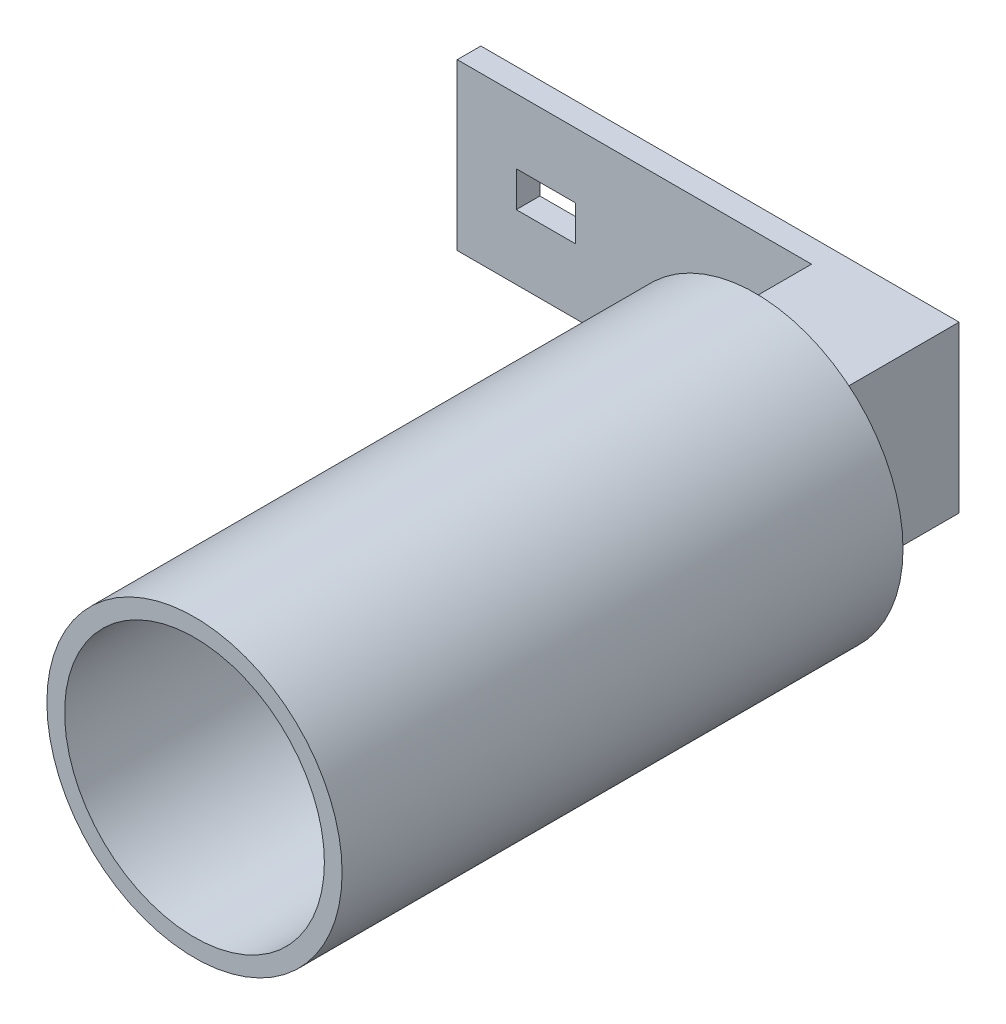
SolidWorks part; units mm, degrees
ref_plane "Plan de face" through (0, 0, 0) normal (0, 0, 1) x (1, 0, 0)
ref_plane "Plan de dessus" through (0, 0, 0) normal (0, 1, 0) x (1, 0, 0)
ref_plane "Plan de droite" through (0, 0, 0) normal (1, 0, 0) x (0, 0, -1)
sketch "Esquisse1" plane through (0, 0, 0) normal (0, 0, 1) x (1, 0, 0)
  circle A0 centre (0, 0) radius 25
  dimension "D1" = 50
extrude "Boss.-Extru.1" add sketch "Esquisse1" along normal blind 95 contours A0
sketch "Esquisse2" plane through (0, 0, 95) normal (0, 0, 1) x (1, 0, 0)
  circle A0 centre (0, 0) radius 22
  circle A1 centre (0, 0) radius 25 construction
  dimension "D1" = 3
extrude "Enlèv. mat.-Extru.1" cut sketch "Esquisse2" against normal blind 70 contours A0
sketch "Esquisse3" plane through (0, 0, 0) normal (0, 0, -1) x (-1, 0, 0)
  line L1 (-10.5, -14) -> (10.5, -14)
  line L2 (-10.5, -14) -> (-10.5, 14)
  line L3 (-10.5, 14) -> (10.5, 14)
  line L4 (10.5, -14) -> (10.5, 14)
  line L5 (-10.5, -14) -> (10.5, 14) construction
  line L6 (-10.5, 14) -> (10.5, -14) construction
  point P0 (0, 0)
  dimension "D1" = 28
  dimension "D2" = 21
extrude "Boss.-Extru.2" add sketch "Esquisse3" along normal blind 24
sketch "Esquisse4" plane through (-10.5, 0, 0) normal (-1, 0, 0) x (0, 0, 1)
  line L0 (0, -14) -> (0, 14) construction
  line L1 (-24, 14) -> (-20, 14)
  line L2 (-24, 14) -> (-24, -14)
  line L3 (-24, -14) -> (-20, -14)
  line L4 (-20, 14) -> (-20, -14)
  line L5 (-24, 14) -> (-20, -14) construction
  line L6 (-24, -14) -> (-20, 14) construction
  line L7 (-24, 14) -> (0, 14) construction
  line L8 (-24, -14) -> (0, -14) construction
  point P0 (-22, 0)
  dimension "D1" = 20
  dimension "D2" = 4
  dimension "D3" = 0
  dimension "D4" = 0
extrude "Boss.-Extru.3" add sketch "Esquisse4" along normal blind 60
sketch "Esquisse5" plane through (0, 0, -24) normal (0, 0, -1) x (-1, 0, 0)
  line L0 (-10.5, -14) -> (70.5, -14) construction
  line L1 (50.5, -3) -> (60.5, -3)
  line L2 (50.5, -3) -> (50.5, 3)
  line L3 (50.5, 3) -> (60.5, 3)
  line L4 (60.5, -3) -> (60.5, 3)
  line L5 (50.5, -3) -> (60.5, 3) construction
  line L6 (50.5, 3) -> (60.5, -3) construction
  line L8 (70.5, 14) -> (70.5, -14) construction
  point P0 (55.5, 0)
  dimension "D1" = 6
  dimension "D2" = 10
  dimension "D3" = 11
  dimension "D4" = 10
extrude "Enlèv. mat.-Extru.2" cut sketch "Esquisse5" against normal up to next
equation "\"taille\"= 3mm"
